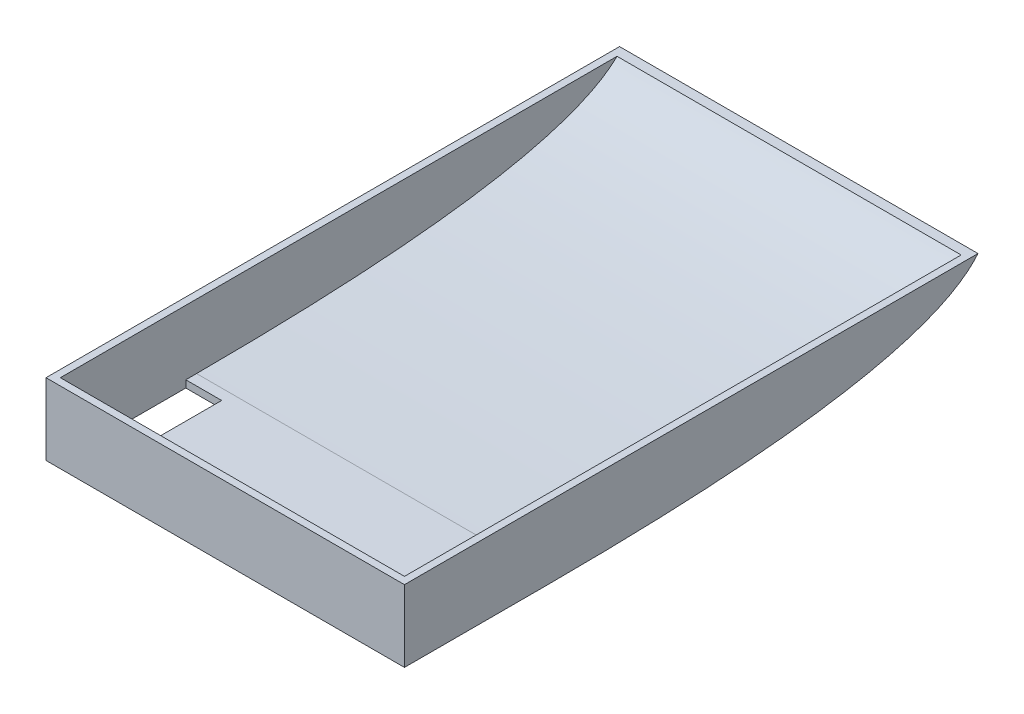
SolidWorks part; units mm, degrees
ref_plane "Front Plane" through (0, 0, 0) normal (0, 0, 1) x (1, 0, 0)
ref_plane "Top Plane" through (0, 0, 0) normal (0, 1, 0) x (1, 0, 0)
ref_plane "Right Plane" through (0, 0, 0) normal (1, 0, 0) x (0, 0, -1)
sketch "Sketch1" plane through (0, 0, 0) normal (1, 0, 0) x (0, 0, -1)
  line L0 (-50.8, 25.4) -> (-50.8, 0)
  line L1 (-50.8, 0) -> (0, 0)
  line L2 (-50.8, 25.4) -> (152.4, 25.4)
  line L3 (0, 0) -> (90.3999, 0.1285) construction
  line L4 (90.3999, 0.1285) -> (138.8723, 8.8623) construction
  line L5 (138.8723, 8.8623) -> (152.4, 25.4) construction
  spline S0 degree 3 poles (0, 0) (90.3999, 0.1285) (138.8723, 8.8623) (152.4, 25.4) knots 0 0 0 0 1 1 1 1
  dimension "D1" = 25.4
  dimension "D2" = 203.2
  dimension "D3" = 50.8
extrude "Boss-Extrude1" add sketch "Sketch1" along normal mid plane 127
shell "Shell1" thickness 2.54 removed face at (0, 25.4, -50.8)
sketch "Sketch4" plane through (0, 25.4, 0) normal (0, 1, 0) x (1, 0, 0)
  line L1 (-60.96, -48.26) -> (-48.26, -48.26)
  line L2 (-60.96, -48.26) -> (-60.96, -3.81)
  line L3 (-60.96, -3.81) -> (-48.26, -3.81)
  line L4 (-48.26, -48.26) -> (-48.26, -3.81)
  line L5 (60.96, -48.26) -> (48.26, -48.26)
  line L6 (60.96, -48.26) -> (60.96, -3.81)
  line L7 (60.96, -3.81) -> (48.26, -3.81)
  line L8 (48.26, -48.26) -> (48.26, -3.81)
  dimension "D1" = 44.45
  dimension "D2" = 12.7
extrude "Cut-Extrude1" cut sketch "Sketch4" against normal through all
